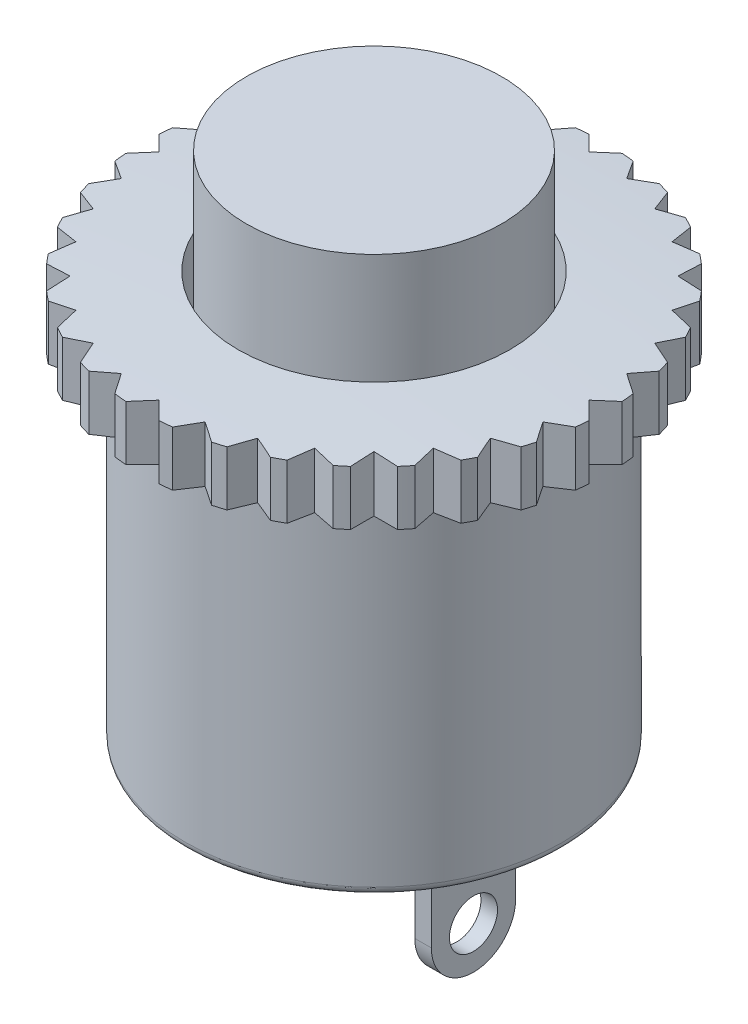
SolidWorks part; units mm, degrees
ref_plane "Front Plane" through (0, 0, 0) normal (0, 0, 1) x (1, 0, 0)
ref_plane "Top Plane" through (0, 0, 0) normal (0, 1, 0) x (1, 0, 0)
ref_plane "Right Plane" through (0, 0, 0) normal (1, 0, 0) x (0, 0, -1)
sketch "Sketch1" plane through (0, 0, 0) normal (0, 0, 1) x (1, 0, 0)
  line L0 (0, 0) -> (-3.85, 0)
  line L1 (-3.85, 0) -> (-3.85, -3.15)
  line L2 (0, 8.3955) -> (0, -10.929) construction
  line L3 (-7, -3.3212) -> (-7, -4.9712)
  line L4 (-7, -4.9712) -> (-5.7, -4.9712)
  line L5 (-5.7, -4.9712) -> (-5.7, -15.4712)
  line L6 (-5.7, -15.4712) -> (0, -15.4712)
  line L7 (0, 0) -> (0, -15.4712)
  arc A0 (-3.85, -3.15) -> (-7, -3.3212) centre (0, -103.0759) ccw
  dimension "D3" = 200
  dimension "D1" = 7.7
  dimension "D2" = 3.15
  dimension "D4" = 14
  dimension "D5" = 1.65
  dimension "D6" = 11.4
  dimension "D7" = 10.5
revolve "Revolve1" add sketch "Sketch1" angle 360 about L2
ref_plane "Plane1" through (0, -3.15, 0) normal (0, -1, 0) x (-1, 0, 0)
sketch "Sketch2" plane through (0, -3.15, 0) normal (0, -1, 0) x (-1, 0, 0)
  circle A0 centre (0, 0) radius 3.85 construction
  circle A1 centre (0, 0) radius 3.85
  circle A2 centre (0, 0) radius 4.1
  dimension "D1" = 0.25
extrude "Cut-Extrude1" cut sketch "Sketch2" along normal blind 3
sketch "Sketch3" plane through (0, -3.15, 0) normal (0, -1, 0) x (-1, 0, 0)
  line L0 (0, 8.7682) -> (0, -1.5786) construction
  line L1 (0, 6.4821) -> (0.5, 6.9821)
  line L2 (0, 6.4821) -> (-0.5, 6.9821)
  circle A0 centre (0, 0) radius 7 construction
  circle A1 centre (0, 0) radius 7
  dimension "D1" = 0.5
  dimension "D2" = 45
extrude "Cut-Extrude2" cut sketch "Sketch3" along normal up to next contours L0 A1 L2 | A1 L0 L1 region at (-0.1676, -3.15, -6.8234) region at (0.1676, -3.15, -6.8234)
ref_axis "Axis1" through (0, -16.2447, 0) along (0, 1, 0)
pattern_circular "CirPattern1" count 32 over 360 about axis through (0, -16.2447, 0) along (0, 1, 0) of "Cut-Extrude2"
sketch "Sketch4" plane through (0, -15.4712, 0) normal (0, -1, 0) x (1, 0, 0)
  circle A4 centre (0, 0) radius 5.2
  circle A5 centre (0, 0) radius 5.2
  dimension "D1" = 0.5
extrude "Cut-Extrude3" cut sketch "Sketch4" against normal blind 0.5
fillet "Fillet1" radius 0.25 1 edges at (0, -15.4712, 5.7)
sketch "Sketch5" plane through (0, -14.9712, 0) normal (0, -1, 0) x (1, 0, 0)
  line L0 (-8.0099, 0) -> (9.6301, 0) construction
  line L1 (0, 9.2819) -> (0, -8.963) construction
  line L2 (-3, 1.27) -> (-2.5, 1.27)
  line L3 (-3, 1.27) -> (-3, -1.27)
  line L4 (-3, -1.27) -> (-2.5, -1.27)
  line L5 (-2.5, 1.27) -> (-2.5, -1.27)
  line L6 (-3, 1.27) -> (-2.5, -1.27) construction
  line L7 (-3, -1.27) -> (-2.5, 1.27) construction
  line L8 (3, 1.27) -> (2.5, 1.27)
  line L9 (3, 1.27) -> (3, -1.27)
  line L10 (3, -1.27) -> (2.5, -1.27)
  line L11 (2.5, 1.27) -> (2.5, -1.27)
  point P1 (-2.75, 0)
  dimension "D1" = 2.54
  dimension "D2" = 0.5
  dimension "D3" = 5
extrude "Boss-Extrude1" add sketch "Sketch5" along normal blind 5
sketch "Sketch6" plane through (3, 0, 0) normal (1, 0, 0) x (0, 0, -1)
  line L0 (0, -19.9712) -> (0, -15.2212) construction
  line L1 (1.27, -19.9712) -> (-1.27, -19.9712) construction
  line L2 (5.7, -15.2212) -> (-5.7, -15.2212) construction
  line L3 (-1.27, -19.9712) -> (-1.27, -14.9712) construction
  line L8 (1.27, -14.9712) -> (-1.27, -14.9712)
  line L9 (-1.27, -14.9712) -> (-1.27, -19.9712)
  line L10 (-1.27, -19.9712) -> (1.27, -19.9712)
  line L11 (1.27, -19.9712) -> (1.27, -14.9712)
  line L12 (1.27, -14.9712) -> (-1.27, -14.9712)
  line L13 (-1.27, -14.9712) -> (-1.27, -19.9712)
  line L14 (-1.27, -19.9712) -> (1.27, -19.9712)
  line L15 (1.27, -19.9712) -> (1.27, -14.9712)
  circle A0 centre (0, -18.7012) radius 1.27
  circle A1 centre (0, -18.7012) radius 0.725
  line M9 (-1.27, -19.9712) -> (1.27, -19.9712)
  line M10 (1.27, -19.9712) -> (1.27, -14.9712)
  dimension "D2" = 1.45
  dimension "D1" = 0
extrude "Cut-Extrude4" cut sketch "Sketch6" against normal up to surface (6 mm away) contours A0 L13 M9 | A0 L14 M10 | L0 A1 | A1 L0 region at (3, -19.6875, -0.9863) region at (3, -19.6875, 0.9863) region at (3, -18.7012, 0.3077) region at (3, -18.7012, -0.3077) up to face at (-3, -17.4712, 0)
